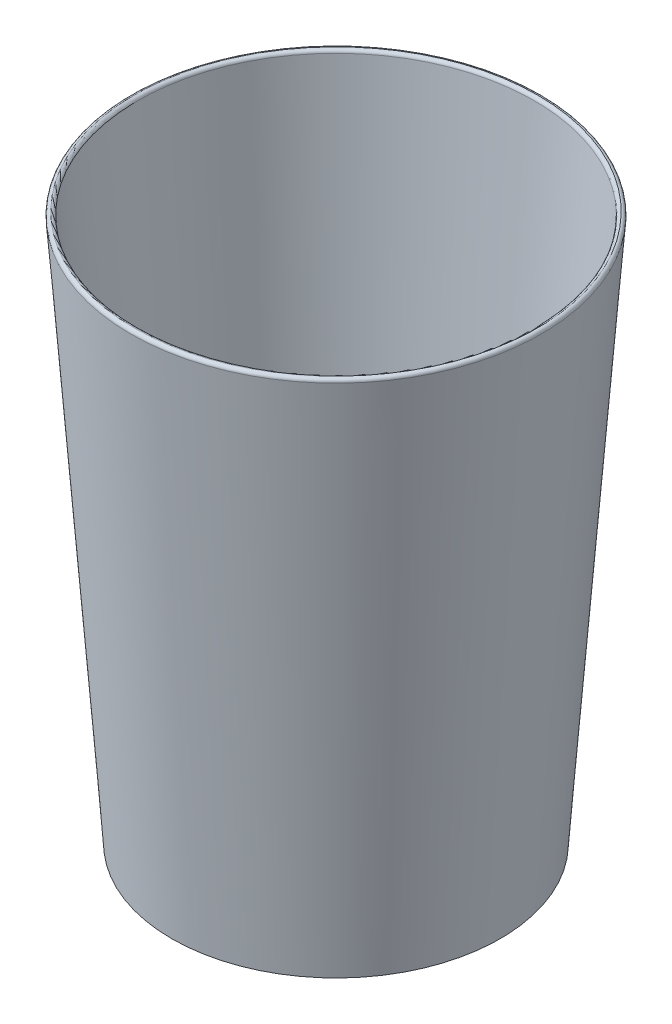
SolidWorks part; units mm, degrees
ref_plane "Alzado" through (0, 0, 0) normal (0, 0, 1) x (1, 0, 0)
ref_plane "Planta" through (0, 0, 0) normal (0, 1, 0) x (1, 0, 0)
ref_plane "Vista lateral" through (0, 0, 0) normal (1, 0, 0) x (0, 0, -1)
sketch "Croquis1" plane through (0, 0, 0) normal (0, 0, 1) x (1, 0, 0)
  line L0 (0, 400) -> (150, 400)
  line L1 (150, 400) -> (120, 0)
  line L2 (120, 0) -> (0, 0)
  line L3 (0, 0) -> (0, 400)
  dimension "D1" = 150
  dimension "D2" = 400
  dimension "D3" = 120
revolve "Revolución1" add sketch "Croquis1" angle 360 about L3
shell "Vaciado1" thickness 5 removed face at (0, 400, -150)
fillet "Redondeo2" radius 2.5 2 edges at (0, 400, 144.986) (0, 400, -150)
